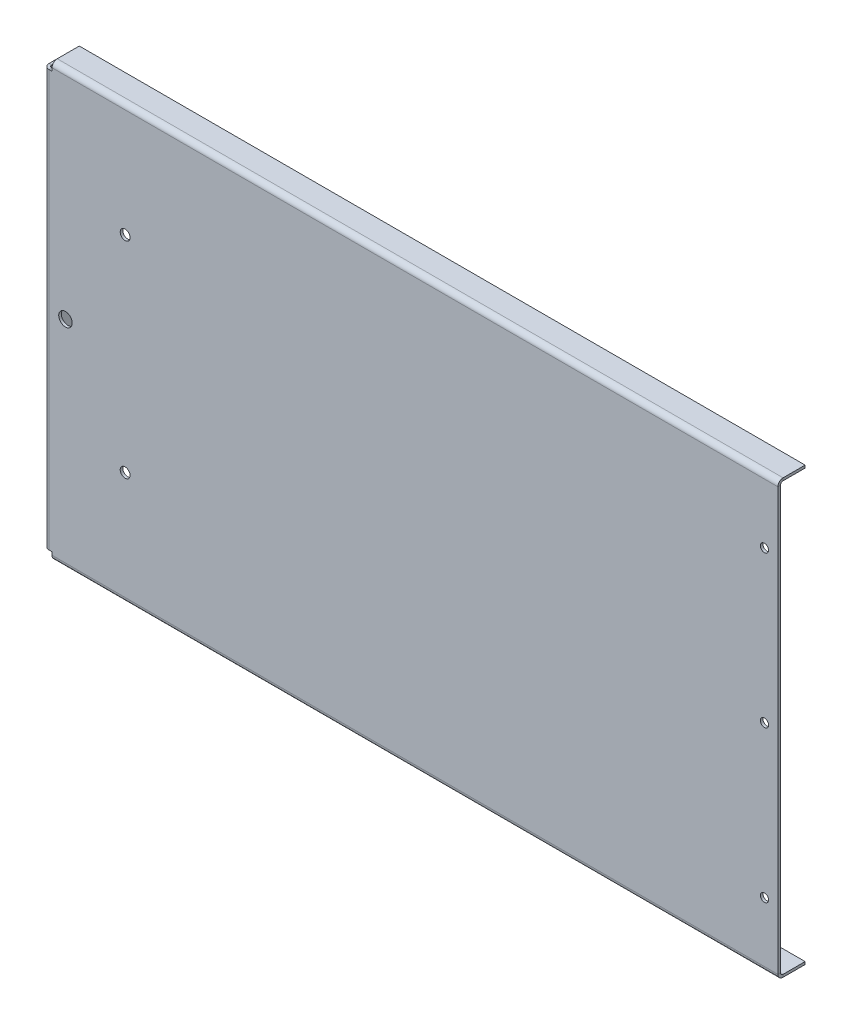
SolidWorks part; units mm, degrees
note: The reader was unsure of these and kept them because the rebuilt part matched: flange length of "Brida de arista1".
ref_plane "Alzado" through (0, 0, 0) normal (0, 0, 1) x (1, 0, 0)
ref_plane "Planta" through (0, 0, 0) normal (0, 1, 0) x (1, 0, 0)
ref_plane "Vista lateral" through (0, 0, 0) normal (1, 0, 0) x (0, 0, -1)
sketch "Croquis1" plane through (0, 0, 0) normal (0, 0, 1) x (1, 0, 0)
  line L1 (-215.519, -127) -> (215.519, -127)
  line L2 (-215.519, -127) -> (-215.519, 127)
  line L3 (-215.519, 127) -> (215.519, 127)
  line L4 (215.519, -127) -> (215.519, 127)
  line L5 (-215.519, -127) -> (215.519, 127) construction
  line L6 (-215.519, 127) -> (215.519, -127) construction
  point P0 (0, 0)
  dimension "D1" = 254
  dimension "D2" = 431.038
base flange "Brida base1" sketch "Croquis1" thickness 1.524 reverse thickness direction no parameters "D1"=1.524
sketch "Croquis6" plane through (0, 0, 0) normal (0, 0, 1) x (1, 0, 0)
  line L1 (-215.519, 127) -> (-210.693, 127)
  line L2 (-215.519, 127) -> (-215.519, 122.174)
  line L3 (-215.519, 122.174) -> (-210.693, 122.174)
  line L4 (-210.693, 127) -> (-210.693, 122.174)
  line L5 (-215.519, -127) -> (-210.693, -127)
  line L6 (-215.519, -127) -> (-215.519, -122.174)
  line L7 (-215.519, -122.174) -> (-210.693, -122.174)
  line L8 (-210.693, -127) -> (-210.693, -122.174)
  dimension "D1" = 4.826
  dimension "D2" = 4.826
extrude "Cortar-Extruir1" cut sketch "Croquis6" against normal up to next normal cut yes
edge flange "Brida de arista1" sketch "Croquis13" flange profiles "Croquis13", "Croquis14", "Croquis15" flange angle 90 flange length 16.002 flange position material inside bend radius 1.524 thickness 1.524 relief rectangular gap distance 1 parameters "D6"=10, "D8"=1
sketch "Croquis13" plane through (0, 127, -1.524) normal (0, 1, 0) x (1, 0, 0)
  line L0 (215.519, 0) -> (-210.693, 0) construction
  line L1 (215.519, 0) -> (-210.693, 0)
  line L2 (-210.693, 0) -> (-210.693, 14.478)
  line L3 (-210.693, 14.478) -> (215.519, 14.478)
  line L4 (215.519, 14.478) -> (215.519, 0)
sketch "Croquis14" plane through (0, -127, -1.524) normal (0, -1, 0) x (-1, 0, 0)
  line L0 (210.693, 0) -> (-215.519, 0) construction
  line L1 (210.693, 0) -> (-215.519, 0)
  line L2 (-215.519, 0) -> (-215.519, 14.478)
  line L3 (-215.519, 14.478) -> (210.693, 14.478)
  line L4 (210.693, 14.478) -> (210.693, 0)
sketch "Croquis15" plane through (-215.519, 0, -1.524) normal (-1, 0, 0) x (0, 1, 0)
  line L0 (122.174, 0) -> (-122.174, 0) construction
  line L1 (122.174, 0) -> (-122.174, 0)
  line L2 (-122.174, 0) -> (-122.174, 14.478)
  line L3 (-122.174, 14.478) -> (122.174, 14.478)
  line L4 (122.174, 14.478) -> (122.174, 0)
bend "Pliegue de arista1" bend radius 1.524 bend angle 90 parameters "D5"=1
bend "Pliegue de arista2" bend radius 1.524 bend angle 90 parameters "D5"=2
bend "Pliegue de arista3" bend radius 1.524 bend angle 90 parameters "D5"=3
sketch "Croquis16" plane through (0, 0, 0) normal (0, 0, 1) x (1, 0, 0)
  line L0 (215.519, -123.952) -> (215.519, 123.952) construction
  line L1 (215.519, 127) -> (-210.693, 127) construction
  line L2 (-210.693, -127) -> (215.519, -127) construction
  circle A0 centre (-202.819, 0) radius 3.9624
  circle A1 centre (-167.767, 60.452) radius 2.8956
  circle A2 centre (-167.767, -60.452) radius 2.8956
  circle A3 centre (207.645, 88.9) radius 2.413
  circle A4 centre (207.645, 0) radius 2.413
  circle A5 centre (207.645, -88.9) radius 2.413
  dimension "D1" = 60.452
  dimension "D2" = 60.452
  dimension "D8" = 4.826
  dimension "D9" = 5.7912
  dimension "D10" = 7.9248
  dimension "D3" = 383.286
  dimension "D4" = 418.338
  dimension "D5" = 38.1
  dimension "D6" = 38.1
  dimension "D7" = 7.874
extrude "Cortar-Extruir2" cut sketch "Croquis16" against normal up to next normal cut yes
sketch "Líneas de pliegue1" plane through (0, 0, 0) normal (0, 1, 0) x (1, 0, 0)
sketch "Cuadro delimitador1" plane through (0, 0, 0) normal (0, 1, 0) x (1, 0, 0)
sheet metal parameters "Chapa metálica1" thickness 1.524 parameters "D1"=1.524
flat pattern "Chapa desplegada1"
sketch "Líneas de pliegue2" plane through (0, 0, 0) normal (0, 1, 0) x (1, 0, 0)
sketch3d "Cuadro delimitador2"
  line L0 (215.519, -190.5, 0) -> (-215.519, -190.5, 0) construction
  line L1 (215.519, 190.5, 0) -> (-215.519, 190.5, 0) construction
  line L2 (215.519, -190.5, 0) -> (215.519, 190.5, 0) construction
  line L3 (-215.519, -190.5, 0) -> (-215.519, 190.5, 0) construction
sheet metal parameters "Chapa metálica2" thickness 1.524 parameters "D1"=1.524
flat pattern "Chapa desplegada1"
sketch "Líneas de pliegue2" plane through (0, 0, 0) normal (0, 1, 0) x (1, 0, 0)
sketch3d "Cuadro delimitador2"
  line L0 (-215.519, -190.5, 0) -> (215.519, -190.5, 0) construction
  line L1 (-215.519, 190.5, 0) -> (215.519, 190.5, 0) construction
  line L2 (-215.519, -190.5, 0) -> (-215.519, 190.5, 0) construction
  line L3 (215.519, -190.5, 0) -> (215.519, 190.5, 0) construction
sheet metal parameters "Chapa metálica3" thickness 1.524 parameters "D1"=1.524
flat pattern "Chapa desplegada1"
sketch "Líneas de pliegue2" plane through (0, 0, 0) normal (0, 0, 1) x (1, 0, 0)
  line L0 (-214.2425, 185.674) -> (-214.2425, -185.674) construction
  line L1 (-210.693, -189.2235) -> (215.519, -189.2235) construction
  line L2 (215.519, 189.2235) -> (-210.693, 189.2235) construction
  line L3 (-214.2425, 185.674) -> (-214.2425, -185.674) construction
  line L4 (-210.693, -189.2235) -> (215.519, -189.2235) construction
  line L5 (215.519, 189.2235) -> (-210.693, 189.2235) construction
sketch3d "Cuadro delimitador2"
  line L0 (-228.968, -203.949, 0) -> (215.519, -203.949, 0) construction
  line L1 (-228.968, 203.949, 0) -> (215.519, 203.949, 0) construction
  line L2 (-228.968, -203.949, 0) -> (-228.968, 203.949, 0) construction
  line L3 (215.519, -203.949, 0) -> (215.519, 203.949, 0) construction
bend of the flat pattern "Aplanar-<Pliegue de arista1>1"
bend of the flat pattern "Aplanar-<Pliegue de arista2>1"
bend of the flat pattern "Aplanar-<Pliegue de arista3>1"
sheet metal parameters "Chapa metálica4" thickness 1.524 parameters "D1"=1.524
flat pattern "Chapa desplegada1"
sketch "Líneas de pliegue2" plane through (0, 0, 0) normal (0, 0, 1) x (1, 0, 0)
  line L0 (-214.2425, 122.174) -> (-214.2425, -122.174) construction
  line L1 (-210.693, -125.7235) -> (215.519, -125.7235) construction
  line L2 (215.519, 125.7235) -> (-210.693, 125.7235) construction
  line L3 (-214.2425, 122.174) -> (-214.2425, -122.174) construction
  line L4 (-210.693, -125.7235) -> (215.519, -125.7235) construction
  line L5 (215.519, 125.7235) -> (-210.693, 125.7235) construction
sketch3d "Cuadro delimitador2"
  line L0 (-228.968, -140.449, 0) -> (215.519, -140.449, 0) construction
  line L1 (-228.968, 140.449, 0) -> (215.519, 140.449, 0) construction
  line L2 (-228.968, -140.449, 0) -> (-228.968, 140.449, 0) construction
  line L3 (215.519, -140.449, 0) -> (215.519, 140.449, 0) construction
bend of the flat pattern "Aplanar-<Pliegue de arista1>1"
bend of the flat pattern "Aplanar-<Pliegue de arista2>1"
bend of the flat pattern "Aplanar-<Pliegue de arista3>1"
equation "\"A\"=10"
equation "\"D1@Croquis1\"=\"A\""
